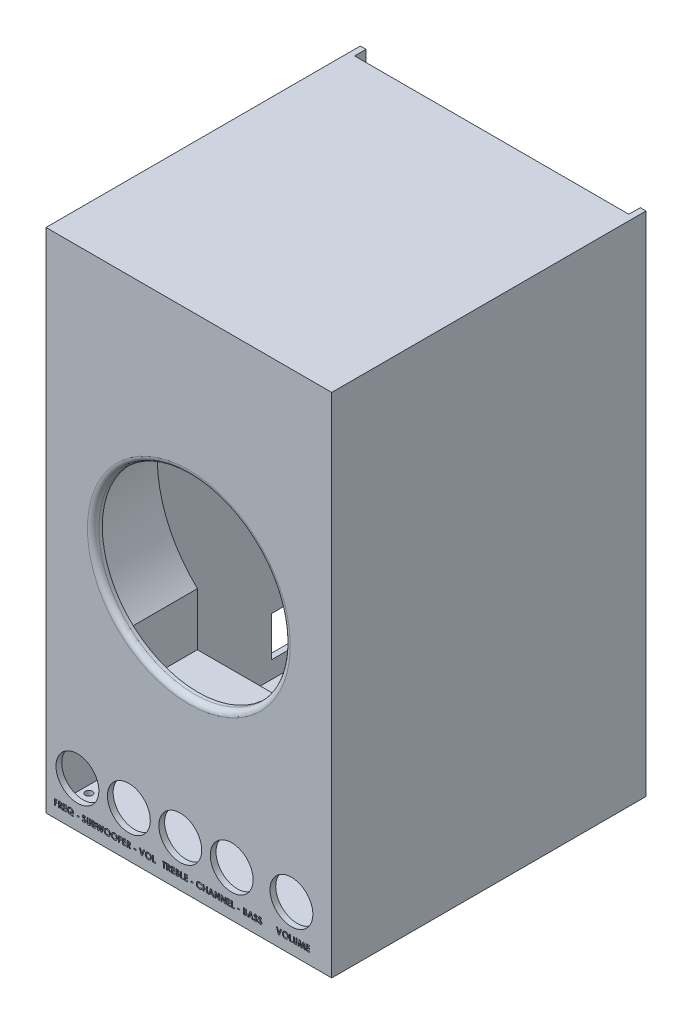
SolidWorks part; units mm, degrees
ref_plane "Front Plane" through (0, 0, 0) normal (0, 0, 1) x (1, 0, 0)
ref_plane "Top Plane" through (0, 0, 0) normal (0, 1, 0) x (1, 0, 0)
ref_plane "Right Plane" through (0, 0, 0) normal (1, 0, 0) x (0, 0, -1)
sketch "Sketch1" plane through (0, 0, 0) normal (1, 0, 0) x (0, 0, -1)
  line L0 (0, 0) -> (110, 0)
  line L1 (110, 0) -> (110, 3)
  line L2 (110, 3) -> (2, 3)
  line L3 (2, 3) -> (2, 34)
  line L7 (0, 177.5) -> (0, 0)
  line L9 (2, 34) -> (27.5, 34)
  line L10 (27.5, 34) -> (27.5, 41)
  line L13 (106, 177.5) -> (0, 177.5)
  line L15 (27.5, 41) -> (33.5, 41)
  line L16 (33.5, 41) -> (33.5, 175.5)
  line L17 (106, 177.5) -> (106, 175.5)
  line L18 (106, 175.5) -> (33.5, 175.5)
  dimension "D1" = 2
  dimension "D2" = 33.5
  dimension "D3" = 3
  dimension "D4" = 136.5
  dimension "D5" = 25.5
  dimension "D6" = 31
  dimension "D7" = 38
  dimension "D8" = 110
  dimension "D9" = 2
  dimension "D10" = 106
extrude "Boss-Extrude1" add sketch "Sketch1" along normal blind 96
sketch "Sketch3" plane through (0, 0, -33.5) normal (0, 0, -1) x (-1, 0, 0)
  line L0 (-48, 41) -> (-48, 42.5) construction
  line L1 (-96, 41) -> (0, 41) construction
  line L5 (-48, 42.5) -> (-48, 93.5) construction
  circle A0 centre (-48, 93.5) radius 44.55
  dimension "D3" = 89.1
  dimension "D1" = 1.5
  dimension "D4" = 51
sketch "Sketch5" plane through (0, 0, -33.5) normal (0, 0, -1) x (-1, 0, 0)
  line L0 (-48, 41) -> (-48, 175.5) construction
  line L1 (-96, 41) -> (0, 41) construction
  line L2 (-78.5, 42.5) -> (-17.5, 42.5)
  line L3 (-96, 41) -> (0, 41) construction
  line L4 (-78.5, 42.5) -> (-78.5, 61.0277)
  line L5 (-78.5, 61.0277) -> (-17.5, 61.0277)
  line L6 (-17.5, 61.0277) -> (-17.5, 42.5)
  line L7 (-63.35, 175.5) -> (-32.65, 175.5)
  line L8 (-32.65, 175.5) -> (-32.65, 135.322)
  line L9 (-32.65, 135.322) -> (-63.35, 135.322)
  line L10 (-63.35, 135.322) -> (-63.35, 175.5)
  circle A0 centre (-48, 93.5) radius 44.55 construction
  dimension "D1" = 61
  dimension "D2" = 30.7
  dimension "D3" = 133
extrude "Cut-Extrude1" cut sketch "Sketch3" against normal blind 31.3
extrude "Cut-Extrude2" cut sketch "Sketch5" against normal blind 31.3
sketch "Sketch7" plane through (0, 0, -2.2) normal (0, 0, -1) x (-1, 0, 0)
  circle A0 centre (-48, 93.5) radius 35.5
  circle A1 centre (-48, 93.5) radius 44.55 construction
  dimension "D1" = 71
extrude "Boss-Extrude2" add sketch "Sketch7" along normal blind 1
sketch "Sketch6" plane through (0, 0, 0) normal (0, 0, 1) x (1, 0, 0)
  circle A0 centre (48, 93.5) radius 33.5
  arc A1 (32.65, 135.322) -> (17.5, 61.0277) centre (48, 93.5) ccw construction
  dimension "D1" = 67
extrude "Cut-Extrude3" cut sketch "Sketch6" against normal through all
fillet "Fillet1" radius 2 1 edges at (81.5, 93.5, 0)
sketch "Sketch8" plane through (0, 0, -2) normal (0, 0, -1) x (-1, 0, 0)
  line L0 (-96, 16) -> (0, 16) construction
  line L1 (-96, 3) -> (-96, 34) construction
  line L2 (0, 3) -> (0, 34) construction
  line L3 (-96, 3) -> (0, 3) construction
  circle A0 centre (-83.9, 16) radius 7.5
  circle A1 centre (-63, 16) radius 7.5
  circle A2 centre (-45, 16) radius 7.5
  circle A3 centre (-27, 16) radius 7.5
  circle A4 centre (-9, 16) radius 7.5
  dimension "D2" = 15
  dimension "D1" = 13
  dimension "D3" = 63
  dimension "D4" = 45
  dimension "D5" = 27
  dimension "D6" = 9
  dimension "D7" = 20.9
extrude "Cut-Extrude4" cut sketch "Sketch8" against normal through all
sketch "Sketch9" plane through (0, 0, -33.5) normal (0, 0, -1) x (-1, 0, 0)
  line L0 (-48, 41) -> (-48, 177.5) construction
  line L1 (-96, 41) -> (0, 41) construction
  line L2 (-96, 177.5) -> (0, 177.5) construction
  line L3 (-71.35, 171) -> (-24.65, 171) construction
  line L5 (-71.35, 141) -> (-24.65, 141) construction
  line L6 (-86.5, 55) -> (-9.5, 55) construction
  circle A0 centre (-71.35, 141) radius 1.15
  circle A1 centre (-24.65, 141) radius 1.15
  circle A2 centre (-71.35, 171) radius 1.15
  circle A3 centre (-24.65, 171) radius 1.15
  circle A4 centre (-86.5, 55) radius 1.15
  circle A5 centre (-9.5, 55) radius 1.15
  point P18 (-48, 171)
  point P19 (-48, 141)
  point P20 (-48, 55)
  dimension "D1" = 2.3
  dimension "D2" = 46.7
  dimension "D3" = 77
  dimension "D4" = 14
  dimension "D5" = 100
  dimension "D6" = 30
extrude "Cut-Extrude5" cut sketch "Sketch9" against normal blind 20
sketch "Sketch10" plane through (96, 0, 0) normal (1, 0, 0) x (0, 0, -1)
  line L1 (0, 177.5) -> (110, 177.5)
  line L2 (0, 177.5) -> (0, 0)
  line L3 (0, 0) -> (110, 0)
  line L4 (110, 177.5) -> (110, 0)
extrude "Boss-Extrude3" add sketch "Sketch10" along normal blind 2
sketch "Sketch11" plane through (0, 0, 0) normal (-1, 0, 0) x (0, 0, 1)
  line L1 (0, 177.5) -> (-110, 177.5)
  line L2 (0, 177.5) -> (0, 0)
  line L3 (0, 0) -> (-110, 0)
  line L4 (-110, 177.5) -> (-110, 0)
extrude "Boss-Extrude4" add sketch "Sketch11" along normal blind 2
sketch "Sketch12" plane through (0, 0, 0) normal (0, 0, 1) x (1, 0, 0)
  text T0 "<b>FREQ - SUBWOOFER - VOL   TREBLE - CHANNEL - BASS      VOLUME</b>" font "Century Gothic" height 2.1
extrude "Cut-Extrude6" cut sketch "Sketch12" against normal blind 1
sketch "Sketch13" plane through (0, 3, 0) normal (0, 1, 0) x (1, 0, 0)
  line L0 (96, 110) -> (96, 2) construction
  line L2 (96, 2) -> (0, 2) construction
  line L3 (0, 110) -> (0, 2) construction
  circle A0 centre (2.5, 10.5) radius 1.25
  circle A1 centre (93.5, 10.5) radius 1.25
  circle A2 centre (93.9, 71.5) radius 1.25
  circle A3 centre (2.5, 71.5) radius 1.25
  dimension "D1" = 2.5
  dimension "D2" = 2.5
  dimension "D3" = 8.5
  dimension "D4" = 8.5
  dimension "D5" = 2.5
  dimension "D6" = 2.5
  dimension "D7" = 2.1
  dimension "D8" = 69.5
  dimension "D9" = 69.5
extrude "Cut-Extrude7" cut sketch "Sketch13" against normal through all
sketch "Sketch14" plane through (0, 0, 0) normal (0, -1, 0) x (1, 0, 0)
  circle A0 centre (2.5, -10.5) radius 2.5
  circle A1 centre (93.5, -10.5) radius 2.5
  circle A2 centre (2.5, -71.5) radius 2.5
  circle A3 centre (93.9, -71.5) radius 2.5
  dimension "D1" = 5
extrude "Cut-Extrude8" cut sketch "Sketch14" against normal blind 1
sketch "Sketch16" plane through (0, 0, 0) normal (1, 0, 0) x (0, 0, -1)
  line L0 (110, 177.5) -> (110, 3) construction
  line L1 (110, 9) -> (77, 9)
  line L2 (110, 9) -> (110, 23)
  line L3 (110, 23) -> (77, 23)
  line L4 (77, 9) -> (77, 23)
  line L5 (110, 3) -> (2, 3) construction
  line L6 (2, 3) -> (2, 34) construction
  dimension "D1" = 14
  dimension "D2" = 6
  dimension "D3" = 75
extrude "Cut-Extrude9" cut sketch "Sketch16" against normal through all
sketch "Sketch17" plane through (0, 0, -27.5) normal (0, 0, -1) x (-1, 0, 0)
  line L0 (-96, 34) -> (0, 34) construction
  line L1 (-96, 41) -> (-91.5, 41)
  line L2 (-96, 41) -> (-96, 34)
  line L3 (-96, 34) -> (-91.5, 34)
  line L4 (-91.5, 41) -> (-91.5, 34)
  line L5 (0, 34) -> (0, 41) construction
  line L6 (0, 41) -> (-4.5, 41)
  line L7 (0, 41) -> (0, 34)
  line L8 (0, 34) -> (-4.5, 34)
  line L9 (-4.5, 41) -> (-4.5, 34)
  line L10 (-96, 41) -> (0, 41) construction
  dimension "D1" = 4.5
  dimension "D2" = 4.5
extrude "Cut-Extrude10" cut sketch "Sketch17" against normal blind 25.5
